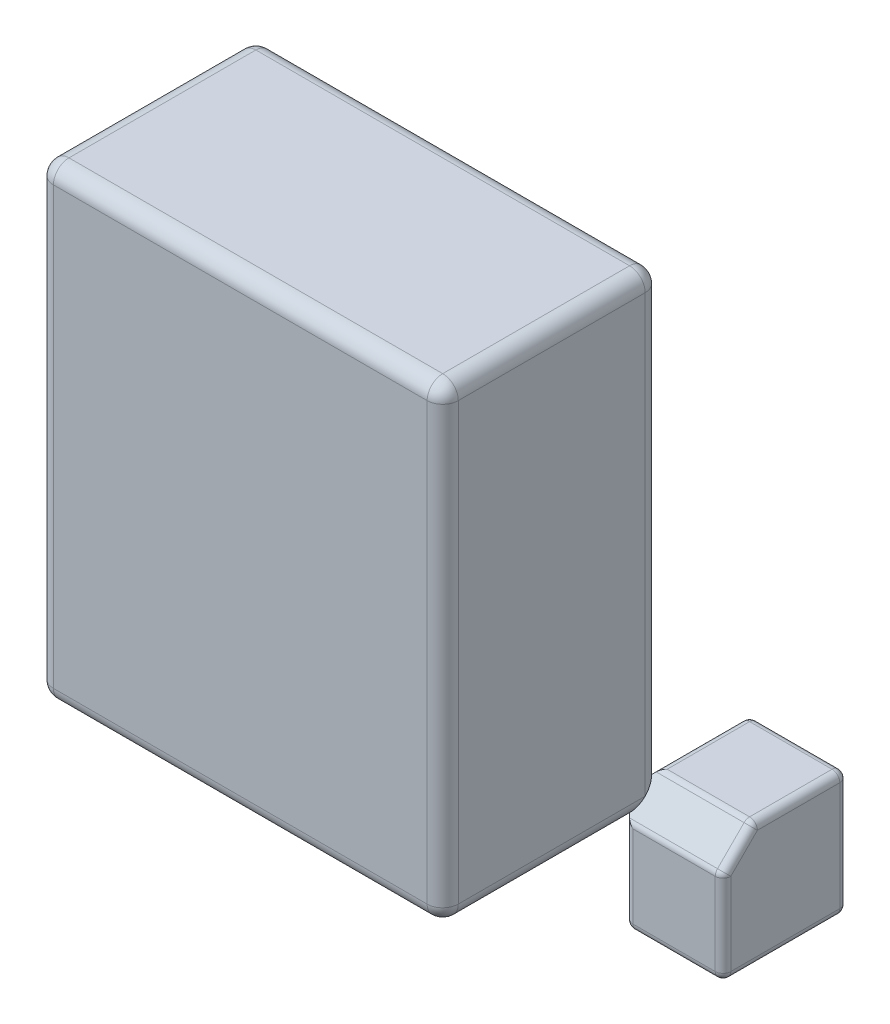
SolidWorks part; units mm, degrees
ref_plane "Front Plane" through (0, 0, 0) normal (0, 0, 1) x (1, 0, 0)
ref_plane "Top Plane" through (0, 0, 0) normal (0, 1, 0) x (1, 0, 0)
ref_plane "Right Plane" through (0, 0, 0) normal (1, 0, 0) x (0, 0, -1)
sketch "Sketch1" plane through (0, 0, 0) normal (0, 0, 1) x (1, 0, 0)
  line L1 (0, 0) -> (26, 0)
  line L2 (0, 0) -> (0, 30)
  line L3 (0, 30) -> (26, 30)
  line L4 (26, 0) -> (26, 30)
  dimension "D1" = 26
  dimension "D2" = 30
extrude "Boss-Extrude1" add sketch "Sketch1" along normal blind 14
sketch "Sketch2" plane through (0, 0, 0) normal (0, 0, -1) x (-1, 0, 0)
  line L0 (-26, 0) -> (-26, 30) construction
  line L1 (-24, 2) -> (-32, 2)
  line L2 (-24, 2) -> (-24, -6)
  line L3 (-24, -6) -> (-32, -6)
  line L4 (-32, 2) -> (-32, -6)
  line L5 (0, 0) -> (-26, 0) construction
  dimension "D1" = 2
  dimension "D2" = 2
  dimension "D3" = 8
  dimension "D4" = 8
shell "Shell1" thickness 1
extrude "Boss-Extrude3" add sketch "Sketch2" along normal blind 6 and the other way blind 2 contours L3 L4 L1 L2
chamfer "Chamfer2" distance 2 angle 45 3 edges at (29, 2, 2) (24, 2, -3) (24, -3, 2)
fillet "Fillet1" radius 1 12 edges at (0, 15, 0) (12, 0, 0) (26, 16, 0) (13, 30, 0) (13, 0, 14) (26, 15, 14) (13, 30, 14) (0, 30, 7) (26, 30, 7) (26, 0, 8) (0, 0, 7) (0, 15, 14)
fillet "Fillet2" radius 0.5 18 edges at (32, -6, -2) (28, -6, -6) (25, -6, 1) (29, -6, 2) (24, -6, -3) (24, -3, -6) (24, 0, -3) (24, -3, 0) (29, 0, 2) (25, 1, -6) (29, 2, -6) (32, 2, -3) (29, 2, 0) (26, 2, -3) (32, -3, 2) (32, -2, -6) (26, -3, 2) (32, 1, 1)
